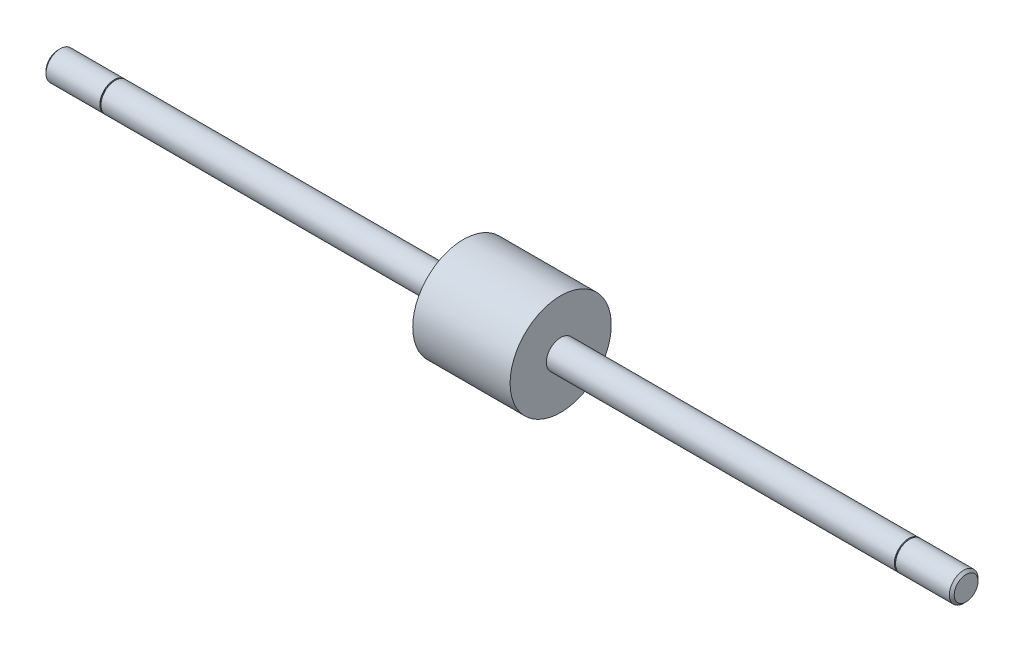
SolidWorks part; units mm, degrees
material "Plain Carbon Steel"
ref_plane "Front Plane" through (0, 0, 0) normal (0, 0, 1) x (1, 0, 0)
ref_plane "Top Plane" through (0, 0, 0) normal (0, 1, 0) x (1, 0, 0)
ref_plane "Right Plane" through (0, 0, 0) normal (1, 0, 0) x (0, 0, -1)
sketch "Sketch1" plane through (0, 0, 0) normal (0, 0, 1) x (1, 0, 0)
  line L0 (0, 0) -> (0, 3.175)
  line L1 (0, 3.175) -> (76.9874, 3.175)
  line L2 (76.9874, 3.175) -> (76.9874, 11.1951)
  line L3 (76.9874, 11.1951) -> (98.5266, 11.1951)
  line L4 (98.5266, 11.1951) -> (98.5266, 0)
  line L5 (98.5266, 0) -> (0, 0)
  line L6 (98.5266, 0) -> (0, 0) construction
revolve "Revolve1" add sketch "Sketch1" angle 360 about L6 reverse direction yes
cosmetic thread "Cosmetic Thread1" parameters "D1"=12.7, "D2"=5.268
sketch "Sketch2" plane through (0, 0, 0) normal (0, 0, 1) x (1, 0, 0)
  line L0 (-12.7, 0) -> (-12.7, 2.634)
  line L1 (-12.7, 2.634) -> (-12.159, 3.175)
  line L2 (-12.159, 3.175) -> (0, 3.175)
  line L3 (0, 3.175) -> (0, 0)
  line L4 (0, 0) -> (-12.7, 0)
  line L5 (0, 0) -> (-12.7, 0) construction
revolve "Revolve2" add sketch "Sketch2" angle 360 about L5 reverse direction yes
ref_plane "Plane1" through (0, 0, 0) normal (1, 0, 0) x (0, 0, -1)
sketch "Sketch3" plane through (0, 0, 0) normal (0, 0, 1) x (1, 0, 0)
  line L0 (98.5266, 0) -> (98.5266, 3.175)
  line L1 (98.5266, 3.175) -> (175.514, 3.175)
  line L2 (175.514, 3.175) -> (175.514, 0)
  line L3 (175.514, 0) -> (98.5266, 0)
  line L4 (175.514, 0) -> (98.5266, 0) construction
revolve "Revolve3" add sketch "Sketch3" angle 360 about L4 reverse direction yes
cosmetic thread "Cosmetic Thread2" parameters "D1"=12.7, "D2"=5.268
sketch "Sketch4" plane through (0, 0, 0) normal (0, 0, 1) x (1, 0, 0)
  line L0 (175.514, 0) -> (175.514, 3.175)
  line L1 (175.514, 3.175) -> (187.673, 3.175)
  line L2 (187.673, 3.175) -> (188.214, 2.634)
  line L3 (188.214, 2.634) -> (188.214, 0)
  line L4 (188.214, 0) -> (175.514, 0)
  line L5 (188.214, 0) -> (175.514, 0) construction
revolve "Revolve4" add sketch "Sketch4" angle 360 about L5 reverse direction yes
ref_plane "Plane2" through (0, 0, 0) normal (1, 0, 0) x (0, 0, -1)
ref_plane "Plane3" through (175.514, 0, 0) normal (1, 0, 0) x (0, 0, -1)
ref_plane "Plane4" through (-12.7, 0, 0) normal (1, 0, 0) x (0, 0, -1)
ref_plane "Plane5" through (188.214, 0, 0) normal (1, 0, 0) x (0, 0, -1)
ref_plane "Plane6" through (175.514, 0, 0) normal (1, 0, 0) x (0, 0, -1)
ref_plane "Plane7" through (0, 0, 0) normal (1, 0, 0) x (0, 0, -1)
sketch "Sketch5" plane through (0, 0, 0) normal (0, 0, 1) x (1, 0, 0)
  line L0 (-0.254, 3.429) -> (-0.254, 2.921)
  line L1 (-0.254, 2.921) -> (0, 2.921)
  line L2 (0, 2.921) -> (0, 3.429)
  line L3 (0, 3.429) -> (-0.254, 3.429)
  line L4 (0, 0) -> (-0.254, 0) construction
revolve "Cut-Revolve1" cut sketch "Sketch5" angle 360 about L4 reverse direction yes
sketch "Sketch6" plane through (0, 0, 0) normal (0, 0, 1) x (1, 0, 0)
  line L0 (175.514, 3.429) -> (175.514, 2.921)
  line L1 (175.514, 2.921) -> (175.768, 2.921)
  line L2 (175.768, 2.921) -> (175.768, 3.429)
  line L3 (175.768, 3.429) -> (175.514, 3.429)
  line L4 (175.768, 0) -> (175.514, 0) construction
revolve "Cut-Revolve2" cut sketch "Sketch6" angle 360 about L4 reverse direction yes
ref_plane "Plane8" through (0, 0, 0) normal (1, 0, 0) x (0, 0, -1)
ref_plane "Plane9" through (-16.764, 0, 0) normal (1, 0, 0) x (0, 0, -1)
ref_plane "dia1 XY" through (0, 0, 0) normal (1, 0, 0) x (0, 0, -1)
ref_plane "dia1 XZ" through (0, 3.175, 0) normal (0, -1, 0) x (-1, 0, 0)
ref_plane "dia1 YZ" through (0, 0, 0) normal (0, 0, -1) x (-1, 0, 0)
ref_axis "dia1 X" through (0, 3.175, 80.9) along (0, 0, -1)
ref_axis "dia1 Y" through (0, -50, 0) along (0, 1, 0)
ref_axis "dia1 Z" through (80.9, 3.175, 0) along (-1, 0, 0)
sketch3d "dia1"
  point P0 (0, 3.175, 0)
ref_plane "dia12 XY" through (0, 0, 0) normal (1, 0, 0) x (0, 0, -1)
ref_plane "dia12 XZ" through (0, 0, 0) normal (0, -1, 0) x (-1, 0, 0)
ref_plane "dia12 YZ" through (0, 0, 11.7602) normal (0, 0, -1) x (-1, 0, 0)
ref_axis "dia12 X" through (0, 0, 80.9) along (0, 0, -1)
ref_axis "dia12 Y" through (0, -50, 11.7602) along (0, 1, 0)
ref_axis "dia12 Z" through (80.9, 0, 11.7602) along (-1, 0, 0)
sketch3d "dia12"
  point P0 (0, 0, 11.7602)
ref_plane "dia2 XY" through (0, 0, 0) normal (1, 0, 0) x (0, 0, -1)
ref_plane "dia2 XZ" through (0, -3.175, 0) normal (0, -1, 0) x (-1, 0, 0)
ref_plane "dia2 YZ" through (0, 0, 0) normal (0, 0, -1) x (-1, 0, 0)
ref_axis "dia2 X" through (0, -3.175, 80.9) along (0, 0, -1)
ref_axis "dia2 Y" through (0, -50, 0) along (0, 1, 0)
ref_axis "dia2 Z" through (80.9, -3.175, 0) along (-1, 0, 0)
sketch3d "dia2"
  point P0 (0, -3.175, 0)
ref_plane "dia22 XY" through (0, 0, 0) normal (1, 0, 0) x (0, 0, -1)
ref_plane "dia22 XZ" through (0, 0, 0) normal (0, -1, 0) x (-1, 0, 0)
ref_plane "dia22 YZ" through (0, 0, -11.7602) normal (0, 0, -1) x (-1, 0, 0)
ref_axis "dia22 X" through (0, 0, 80.9) along (0, 0, -1)
ref_axis "dia22 Y" through (0, -50, -11.7602) along (0, 1, 0)
ref_axis "dia22 Z" through (80.9, 0, -11.7602) along (-1, 0, 0)
sketch3d "dia22"
  point P0 (0, 0, -11.7602)
ref_plane "rl1 XY" through (-12.7, 0, 0) normal (1, 0, 0) x (0, 0, -1)
ref_plane "rl1 XZ" through (0, 0, 0) normal (0, -1, 0) x (-1, 0, 0)
ref_plane "rl1 YZ" through (0, 0, 0) normal (0, 0, -1) x (-1, 0, 0)
ref_axis "rl1 X" through (-12.7, 0, 80.9) along (0, 0, -1)
ref_axis "rl1 Y" through (-12.7, -50, 0) along (0, 1, 0)
ref_axis "rl1 Z" through (80.9, 0, 0) along (-1, 0, 0)
sketch3d "rl1"
  point P0 (-12.7, 0, 0)
ref_plane "rl1_der XY" through (188.214, 0, 0) normal (1, 0, 0) x (0, 0, -1)
ref_plane "rl1_der XZ" through (0, 0, 0) normal (0, -1, 0) x (-1, 0, 0)
ref_plane "rl1_der YZ" through (0, 0, 0) normal (0, 0, -1) x (-1, 0, 0)
ref_axis "rl1_der X" through (188.214, 0, 80.9) along (0, 0, -1)
ref_axis "rl1_der Y" through (188.214, -50, 0) along (0, 1, 0)
ref_axis "rl1_der Z" through (80.9, 0, 0) along (-1, 0, 0)
sketch3d "rl1_der"
  point P0 (188.214, 0, 0)
ref_plane "rl2 XY" through (0, 0, 0) normal (1, 0, 0) x (0, 0, -1)
ref_plane "rl2 XZ" through (0, 0, 0) normal (0, -1, 0) x (-1, 0, 0)
ref_plane "rl2 YZ" through (0, 0, 0) normal (0, 0, -1) x (-1, 0, 0)
ref_axis "rl2 X" through (0, 0, 80.9) along (0, 0, -1)
ref_axis "rl2 Y" through (0, -50, 0) along (0, 1, 0)
ref_axis "rl2 Z" through (80.9, 0, 0) along (-1, 0, 0)
sketch3d "rl2"
  point P0 (0, 0, 0)
ref_plane "rl2_der XY" through (175.514, 0, 0) normal (1, 0, 0) x (0, 0, -1)
ref_plane "rl2_der XZ" through (0, 0, 0) normal (0, -1, 0) x (-1, 0, 0)
ref_plane "rl2_der YZ" through (0, 0, 0) normal (0, 0, -1) x (-1, 0, 0)
ref_axis "rl2_der X" through (175.514, 0, 80.9) along (0, 0, -1)
ref_axis "rl2_der Y" through (175.514, -50, 0) along (0, 1, 0)
ref_axis "rl2_der Z" through (80.9, 0, 0) along (-1, 0, 0)
sketch3d "rl2_der"
  point P0 (175.514, 0, 0)
ref_plane "rod_cp XY" through (0, 0, 0) normal (1, 0, 0) x (0, 0, -1)
ref_plane "rod_cp XZ" through (0, 0, 0) normal (0, -1, 0) x (-1, 0, 0)
ref_plane "rod_cp YZ" through (0, 0, 0) normal (0, 0, -1) x (-1, 0, 0)
ref_axis "rod_cp X" through (0, 0, 80.9) along (0, 0, -1)
ref_axis "rod_cp Y" through (0, -50, 0) along (0, 1, 0)
ref_axis "rod_cp Z" through (80.9, 0, 0) along (-1, 0, 0)
sketch3d "rod_cp"
  point P0 (0, 0, 0)
ref_plane "stroke1 XY" through (0, 0, 0) normal (1, 0, 0) x (0, 0, -1)
ref_plane "stroke1 XZ" through (0, 0, 0) normal (0, -1, 0) x (-1, 0, 0)
ref_plane "stroke1 YZ" through (0, 0, 0) normal (0, 0, -1) x (-1, 0, 0)
ref_axis "stroke1 X" through (0, 0, 80.9) along (0, 0, -1)
ref_axis "stroke1 Y" through (0, -50, 0) along (0, 1, 0)
ref_axis "stroke1 Z" through (80.9, 0, 0) along (-1, 0, 0)
sketch3d "stroke1"
  point P0 (0, 0, 0)
ref_plane "thd1 XY" through (-12.7, 0, 0) normal (1, 0, 0) x (0, 0, -1)
ref_plane "thd1 XZ" through (0, 3.175, 0) normal (0, -1, 0) x (-1, 0, 0)
ref_plane "thd1 YZ" through (0, 0, 0) normal (0, 0, -1) x (-1, 0, 0)
ref_axis "thd1 X" through (-12.7, 3.175, 80.9) along (0, 0, -1)
ref_axis "thd1 Y" through (-12.7, -50, 0) along (0, 1, 0)
ref_axis "thd1 Z" through (80.9, 3.175, 0) along (-1, 0, 0)
sketch3d "thd1"
  point P0 (-12.7, 3.175, 0)
ref_plane "thd2 XY" through (-12.7, 0, 0) normal (1, 0, 0) x (0, 0, -1)
ref_plane "thd2 XZ" through (0, -3.175, 0) normal (0, -1, 0) x (-1, 0, 0)
ref_plane "thd2 YZ" through (0, 0, 0) normal (0, 0, -1) x (-1, 0, 0)
ref_axis "thd2 X" through (-12.7, -3.175, 80.9) along (0, 0, -1)
ref_axis "thd2 Y" through (-12.7, -50, 0) along (0, 1, 0)
ref_axis "thd2 Z" through (80.9, -3.175, 0) along (-1, 0, 0)
sketch3d "thd2"
  point P0 (-12.7, -3.175, 0)
ref_plane "to_rod_clevis XY" through (-16.764, 0, 0) normal (1, 0, 0) x (0, 0, -1)
ref_plane "to_rod_clevis XZ" through (0, 0, 0) normal (0, -1, 0) x (-1, 0, 0)
ref_plane "to_rod_clevis YZ" through (0, 0, 0) normal (0, 0, -1) x (-1, 0, 0)
ref_axis "to_rod_clevis X" through (-16.764, 0, 80.9) along (0, 0, -1)
ref_axis "to_rod_clevis Y" through (-16.764, -50, 0) along (0, 1, 0)
ref_axis "to_rod_clevis Z" through (80.9, 0, 0) along (-1, 0, 0)
sketch3d "to_rod_clevis"
  point P0 (-16.764, 0, 0)
